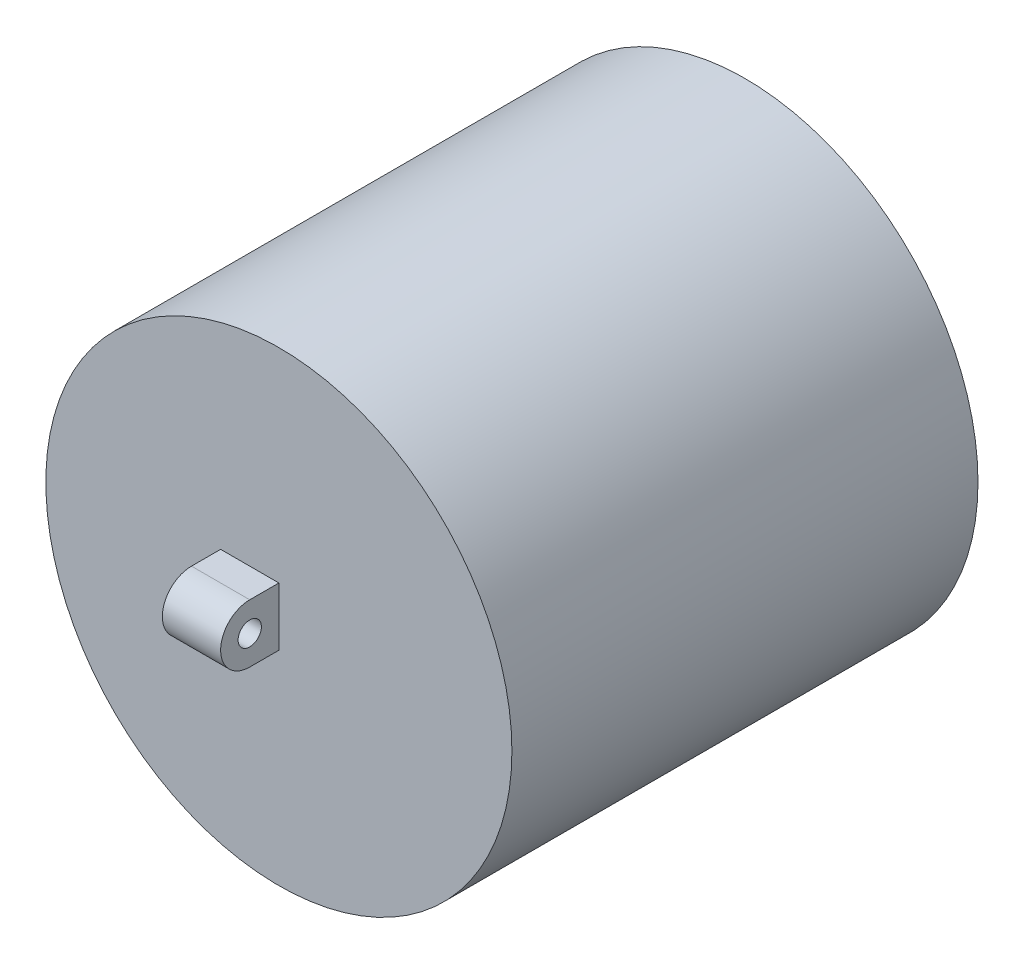
SolidWorks part; units mm, degrees
ref_plane "Front Plane" through (0, 0, 0) normal (0, 0, 1) x (1, 0, 0)
ref_plane "Top Plane" through (0, 0, 0) normal (0, 1, 0) x (1, 0, 0)
ref_plane "Right Plane" through (0, 0, 0) normal (1, 0, 0) x (0, 0, -1)
sketch "Sketch2" plane through (0, 0, 0) normal (0, 0, 1) x (1, 0, 0)
  circle A0 centre (0, 0) radius 12.7
  dimension "D1" = 25.4
extrude "Boss-Extrude1" add sketch "Sketch2" along normal blind 25.4
sketch "Sketch3" plane through (0, 0, 25.4) normal (0, 0, 1) x (1, 0, 0)
  line L0 (0, 1.5875) -> (0, -1.5875)
  line L1 (0, 1.5875) -> (-3.175, 1.5875)
  line L2 (-3.175, 1.5875) -> (-3.175, -1.5875)
  line L3 (-3.175, -1.5875) -> (0, -1.5875)
  point P4 (0, 0)
  dimension "D1" = 3.175
  dimension "D2" = 3.175
extrude "Boss-Extrude2" add sketch "Sketch3" along normal blind 3.175
sketch "Sketch4" plane through (-3.175, 0, 0) normal (-1, 0, 0) x (0, 0, 1)
  line L0 (28.575, -1.5875) -> (25.4, -1.5875) construction
  line L1 (28.575, 1.5875) -> (25.4, 1.5875) construction
  arc A0 (26.9875, 1.5875) -> (26.9875, -1.5875) centre (26.9875, 0) cw
  dimension "D1" = 1.5875
extrude "Cut-Extrude1" cut sketch "Sketch4" against normal blind 3.175 and the other way through all
ref_point "Point1"
sketch "Sketch6" plane through (0, 0, 0) normal (1, 0, 0) x (0, 0, -1)
  circle A0 centre (-26.9875, 0) radius 0.635
  dimension "D1" = 1.27
extrude "Cut-Extrude2" cut sketch "Sketch6" against normal blind 2.54
